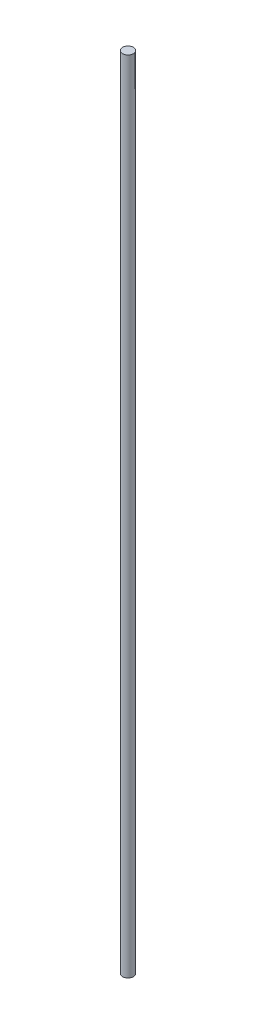
SolidWorks part; units mm, degrees
material "Plain Carbon Steel"
ref_plane "Front Plane" through (0, 0, 0) normal (0, 0, 1) x (1, 0, 0)
ref_plane "Top Plane" through (0, 0, 0) normal (0, 1, 0) x (1, 0, 0)
ref_plane "Right Plane" through (0, 0, 0) normal (1, 0, 0) x (0, 0, -1)
sketch "Sketch1" plane through (0, 0, 0) normal (0, 1, 0) x (1, 0, 0)
  circle A0 centre (0, 0) radius 1
  dimension "D1" = 2
extrude "Boss-Extrude1" add sketch "Sketch1" along normal blind 145.8
